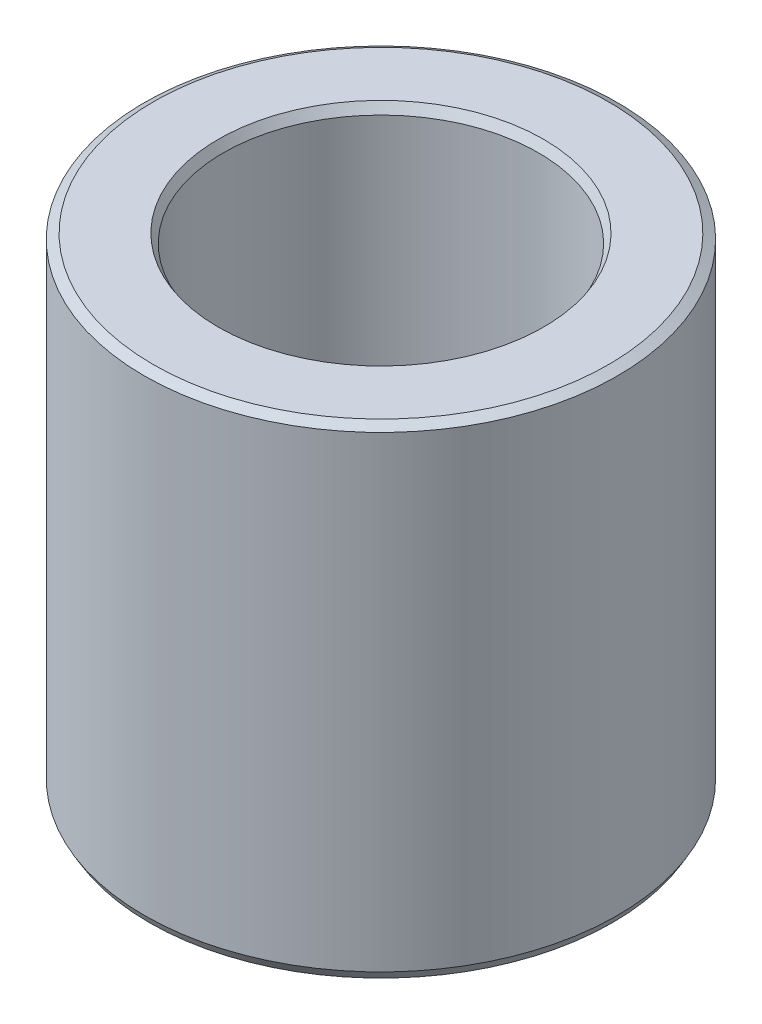
SolidWorks part; units mm, degrees
ref_plane "Front Plane" through (0, 0, 0) normal (0, 0, 1) x (1, 0, 0)
ref_plane "Top Plane" through (0, 0, 0) normal (0, 1, 0) x (1, 0, 0)
ref_plane "Right Plane" through (0, 0, 0) normal (1, 0, 0) x (0, 0, -1)
sketch "Sketch1" plane through (0, 0, 0) normal (0, 1, 0) x (1, 0, 0)
  circle A0 centre (0, 0) radius 32.5
  dimension "SLEEVE_OD" = 65
extrude "Boss-Extrude1" add sketch "Sketch1" along normal blind 66.1181
sketch "Sketch2" plane through (0, 0, 0) normal (0, 1, 0) x (1, 0, 0)
  circle A0 centre (0, 0) radius 21.6282
  dimension "BORE_D" = 43.2565
extrude "Cut-Extrude1" cut sketch "Sketch2" along normal through all
chamfer "Chamfer1" distance 0.7155 angle 60 4 edges at (0, 66.1181, 21.6282) (0, 0, 21.6282) (0, 0, 32.5) (0, 66.1181, 32.5) first distance on face at (0, 66.1181, 21.6282) first distance on face at (0, 0, 21.6282) first distance on face at (0, 66.1181, 32.5)
